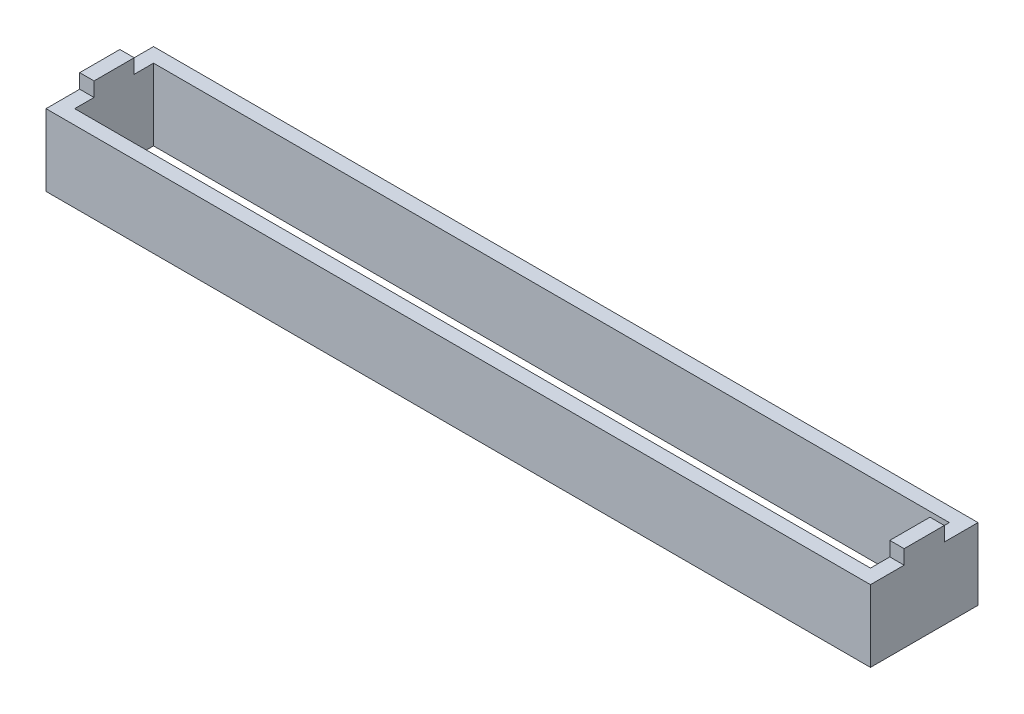
SolidWorks part; units mm, degrees
ref_plane "Front Plane" through (0, 0, 0) normal (0, 0, 1) x (1, 0, 0)
ref_plane "Top Plane" through (0, 0, 0) normal (0, 1, 0) x (1, 0, 0)
ref_plane "Right Plane" through (0, 0, 0) normal (1, 0, 0) x (0, 0, -1)
sketch "Sketch1" plane through (0, 0, 0) normal (0, 1, 0) x (1, 0, 0)
  line L1 (-57.5, -7.5) -> (57.5, -7.5)
  line L2 (-57.5, -7.5) -> (-57.5, 7.5)
  line L3 (-57.5, 7.5) -> (57.5, 7.5)
  line L4 (57.5, -7.5) -> (57.5, 7.5)
  line L5 (-57.5, -7.5) -> (57.5, 7.5) construction
  line L6 (-57.5, 7.5) -> (57.5, -7.5) construction
  line L7 (-55.5, -5.5) -> (55.5, -5.5)
  line L8 (-55.5, -5.5) -> (-55.5, 5.5)
  line L9 (-55.5, 5.5) -> (55.5, 5.5)
  line L10 (55.5, -5.5) -> (55.5, 5.5)
  line L11 (-55.5, -5.5) -> (55.5, 5.5) construction
  line L12 (-55.5, 5.5) -> (55.5, -5.5) construction
  point P0 (0, 0)
  point P6 (0, 0)
  dimension "D1" = 115
  dimension "D2" = 15
  dimension "D3" = 2
  dimension "D4" = 2
extrude "Boss-Extrude1" add sketch "Sketch1" along normal blind 10
sketch "Sketch2" plane through (0, 10, 0) normal (0, 1, 0) x (1, 0, 0)
  line L0 (-57.5, 7.5) -> (-57.5, -7.5) construction
  line L1 (-57.5, -2.8) -> (-55.5, -2.8)
  line L2 (-57.5, -2.8) -> (-57.5, 2.8)
  line L3 (-57.5, 2.8) -> (-55.5, 2.8)
  line L4 (-55.5, -2.8) -> (-55.5, 2.8)
  line L5 (-55.5, 5.5) -> (-55.5, -5.5) construction
  line L6 (-5.5, 0) -> (5.5, 0) construction
  line L7 (55.5, -5.5) -> (55.5, 5.5) construction
  line L8 (55.5, 2.8) -> (57.5, 2.8)
  line L9 (55.5, 2.8) -> (55.5, -2.8)
  line L10 (55.5, -2.8) -> (57.5, -2.8)
  line L11 (57.5, 2.8) -> (57.5, -2.8)
  line L12 (57.5, -7.5) -> (57.5, 7.5) construction
  point P10 (-55.5, 0)
  point P13 (-55.5, 0)
  point P14 (0, 0)
  point P21 (0, 0)
  dimension "D1" = 5.6
extrude "Boss-Extrude2" add sketch "Sketch2" along normal blind 2
